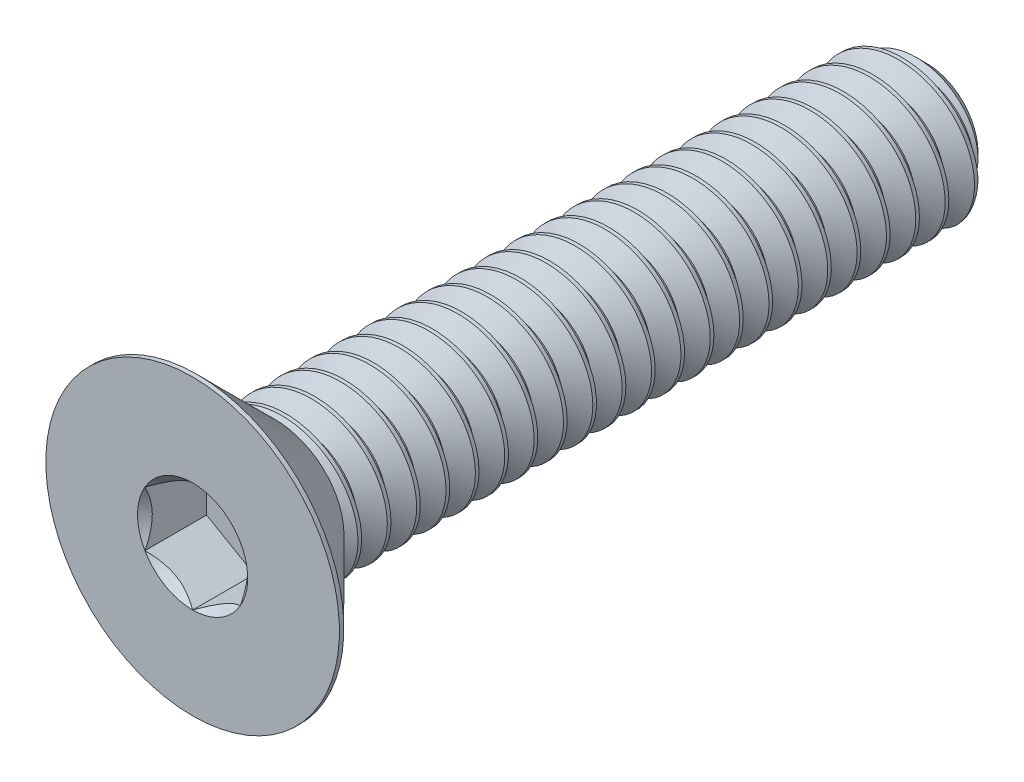
SolidWorks part; units mm, degrees
ref_plane "Front" through (0, 0, 0) normal (0, 0, 1) x (1, 0, 0)
ref_plane "Top" through (0, 0, 0) normal (0, 1, 0) x (1, 0, 0)
ref_plane "Right" through (0, 0, 0) normal (1, 0, 0) x (0, 0, -1)
sketch "Sketch11" plane through (0, 0, 0) normal (1, 0, 0) x (0, 0, -1)
  line L0 (-5, 2) -> (5, 2) construction
  line L5 (-5, 2) -> (-5, -2) construction
  line L6 (5, 1) -> (5, -1) construction
  line L7 (-4.99, 0.65) -> (-4.99, -0.65) construction
  line L8 (4.975, 1.0433) -> (5.375, 1.0433) construction
  line L9 (5.375, 1.0433) -> (5.175, 0.6969) construction
  line L10 (5.175, 0.6969) -> (4.975, 1.0433) construction
  line L11 (5.15, 0.7402) -> (5.2, 0.7402) construction
  line L12 (5.175, 0.7402) -> (5.175, 0.6969) construction
  line L13 (4.9875, 1.0217) -> (5.3625, 1.0217) construction
  line L14 (5.175, 1.0433) -> (5.175, 1) construction
  line L15 (5, 1) -> (5.35, 1) construction
  line L17 (-4.94, 2) -> (-2.94, 0) construction
  line L18 (-2.94, 0) -> (-4.94, -2) construction
  point P3 (-3.8, 2)
  point P8 (0, 2)
  point P21 (5.175, 1.0217)
  point P26 (-5, 0)
  point P28 (-4.99, 0)
  point P29 (5, 0)
  dimension "Length" = 10
  dimension "Head Diameter" = 4
  dimension "Thread Major Diameter" = 2
  dimension "Head Height" = 1.2
  dimension "Drive Size" = 1.3
  dimension "Thread Pitch" = 0.4
  dimension "D1" = 0.05
  dimension "D2" = 0.01
  dimension "D3" = 0.06
  dimension "Countersink Angle" = 90
sketch "Sketch1" plane through (0, 0, 0) normal (1, 0, 0) x (0, 0, -1)
  line L2 (-3.8, 1) -> (5, 1)
  line L3 (5, 1) -> (5, 0)
  line L4 (-4.16, 1) -> (-4.16, 0)
  line L5 (-3.8, 1) -> (-4.16, 1)
  line L6 (-5, 2) -> (-5, -2) construction
  line L7 (5, 1) -> (5, -1) construction
  line L8 (-4.16, 0) -> (5, 0)
  dimension "D1" = 0.84
revolve "Revolve1" add sketch "Sketch1" angle 360 mid plane about L8
chamfer "Chamfer1" distance 0.3 angle 45 1 edges at (0, -1, -5)
sketch "Sketch7" plane through (0, 0, 0) normal (1, 0, 0) x (0, 0, -1)
  line L2 (-5, 2) -> (-4.94, 2)
  line L5 (-3.8, 0.86) -> (-3.8, 0)
  line L6 (-5, 2) -> (-5, 0)
  line L8 (-5, 2) -> (-5, -2) construction
  line L9 (-5, 0) -> (-3.8, 0)
  line L12 (-4.94, 2) -> (-3.8, 0.86)
  line L13 (-4.94, 2) -> (-2.94, 0) construction
revolve "Revolve2" add sketch "Sketch7" angle 360 mid plane about L9 region at (0, 0.7698, 4.4817)
ref_plane "Plane1" through (0, 0, 3.8) normal (0, 0, 1) x (1, 0, 0)
sketch "Sketch5" plane through (0, 0, 5) normal (0, 0, 1) x (1, 0, 0)
  line L1 (0.65, -0.3753) -> (0.65, 0.3753)
  line L2 (0.65, 0.3753) -> (0, 0.7506)
  line L3 (0, 0.7506) -> (-0.65, 0.3753)
  line L4 (-0.65, 0.3753) -> (-0.65, -0.3753)
  line L5 (-0.65, -0.3753) -> (0, -0.7506)
  line L6 (0, -0.7506) -> (0.65, -0.3753)
  circle A0 centre (0, 0) radius 0.65 construction
extrude "Cut-Extrude2" cut sketch "Sketch5" against normal blind 0.84
sketch "Sketch6" plane through (0, 0, 5) normal (0, 0, -1) x (-1, 0, 0)
  circle A0 centre (0, 0) radius 0.7506
extrude "Cut-Extrude3" cut sketch "Sketch6" along normal blind 0.84 draft 45
sketch "Sketch12" plane through (0, 0, -5) normal (0, 0, -1) x (-1, 0, 0)
  circle A0 centre (0, 0) radius 1 construction
  circle A1 centre (0, 0) radius 1
curve "Helix/Spiral1" pitch 0.4 height 10 radius 1 centre (0, 0, -5) axis (0, 0, 1) start towards (0, 1, 0)
sketch "Sketch13" plane through (0, 0, 0) normal (1, 0, 0) x (0, 0, -1)
  line L0 (4.9875, 1.0217) -> (5.3625, 1.0217)
  line L1 (5.3625, 1.0217) -> (5.2, 0.7402)
  line L2 (5.2, 0.7402) -> (5.15, 0.7402)
  line L3 (5.15, 0.7402) -> (4.9875, 1.0217)
sweep "Cut-Sweep1" cut profiles "Sketch13" path "Helix/Spiral1" align with end faces yes
combine bodies "Combine1" operation type add bodies to combine 113 127
equation "\"D1@Chamfer1\"=\"Thread Pitch@Sketch11\" * .75"
equation "\"D1@Cut-Extrude2\"= \"Head Height@Sketch11\" * .7"
equation "\"D1@Cut-Extrude3\" = \"D1@Cut-Extrude2\""
equation "\"D1@Sketch11\"=\"Thread Pitch@Sketch11\"/8"
equation "\"D3@Sketch11\"=\"Head Height@Sketch11\"*.05"
equation "\"D4@Helix/Spiral1\"=\"Thread Pitch@Sketch11\""
equation "\"D1@Sketch1\"=\"Head Height@Sketch11\"*.7"
equation "\"D3@Helix/Spiral1\"=\"Length@Sketch11\""
